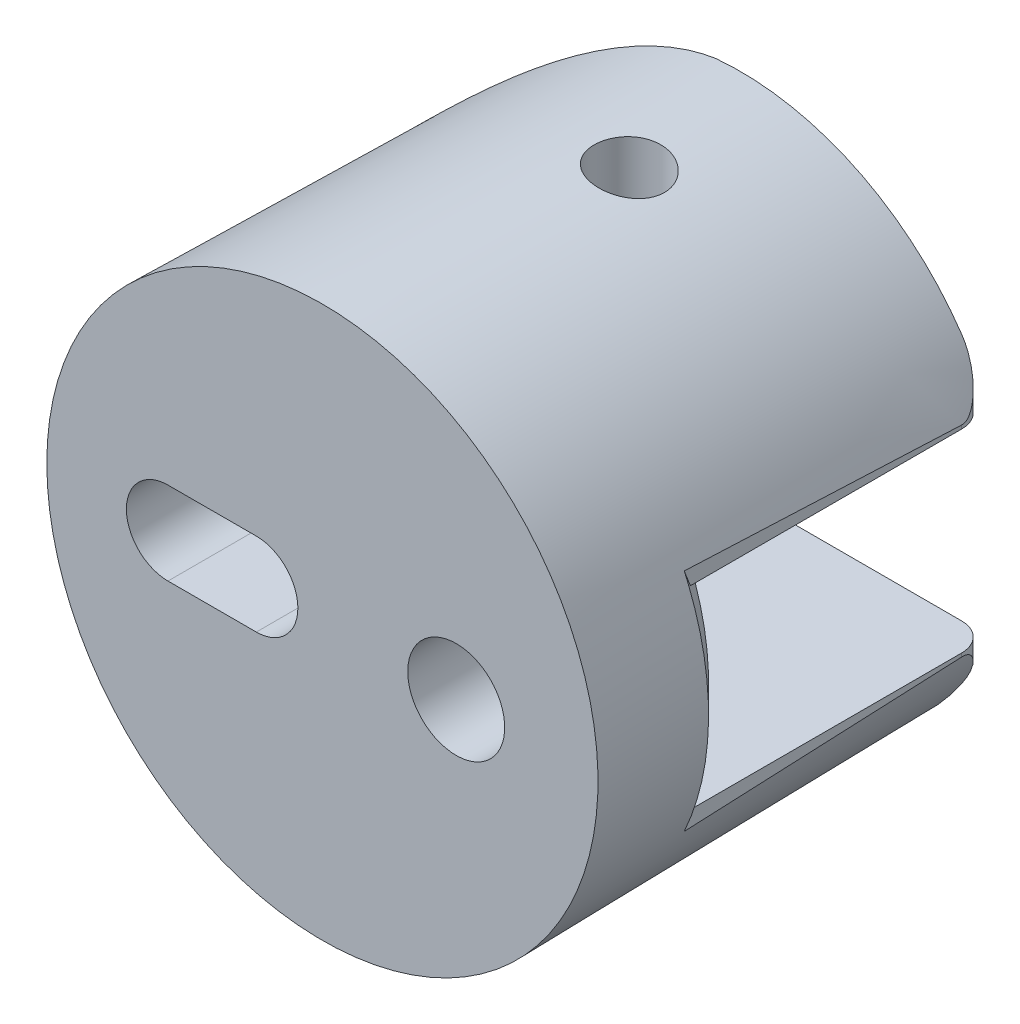
SolidWorks part; units mm, degrees
ref_plane "Plan de face" through (0, 0, 0) normal (0, 0, 1) x (1, 0, 0)
ref_plane "Plan de dessus" through (0, 0, 0) normal (0, 1, 0) x (1, 0, 0)
ref_plane "Plan de droite" through (0, 0, 0) normal (1, 0, 0) x (0, 0, -1)
sketch "Sketch1" plane through (0, 0, 0) normal (0, 0, 1) x (1, 0, 0)
  circle A0 centre (0, 0) radius 10
  dimension "D1" = 20
extrude "Boss-Extrude1" add sketch "Sketch1" along normal blind 18
sketch "Sketch2" plane through (0, 0, 0) normal (0, 1, 0) x (1, 0, 0)
  line L0 (-8, -10) -> (-16.4398, -10)
  line L1 (-16.4398, -10) -> (-16.4398, 10.405)
  line L2 (-16.4398, 10.405) -> (23.4224, 10.405)
  line L3 (23.4224, 10.405) -> (23.4224, -10)
  line L4 (23.4224, -10) -> (9, -10)
  line L5 (-10, 0) -> (-10, -18) construction
  line L6 (-10, -18) -> (10, -18) construction
  line L7 (9, -10) -> (9, 0)
  line L8 (10, 0) -> (-10, 0) construction
  line L9 (9, 0) -> (-0.88, 0)
  line L10 (-8, -10) -> (-7.3114, -5.8406)
  arc A0 (-7.3114, -5.8406) -> (-0.88, 0) centre (-0.4054, -6.9839) cw
  dimension "D5" = 7
  dimension "D1" = 2
  dimension "D2" = 8
  dimension "D3" = 17
  dimension "D4" = 9.88
  dimension "D6" = 80.6
  dimension "D7" = 4.216
extrude "Cut-Extrude1" cut sketch "Sketch2" against normal blind 18 and the other way blind 18 contours L10 A0 L9 L7 L4 L3 L2 L1 L0 region at (4.0327, 0, -1.4851)
sketch "Sketch3" plane through (0, 0, 0) normal (0, 1, 0) x (1, 0, 0)
  line L0 (-10, -18) -> (10, -18) construction
  line L1 (10, -18) -> (10, -10) construction
  circle A0 centre (1, -5) radius 1.25
  dimension "D3" = 2.5
  dimension "D1" = 13
  dimension "D2" = 9
extrude "Cut-Extrude2" cut sketch "Sketch3" against normal mid plane 24
sketch "Sketch4" plane through (0, 0, 18) normal (0, 0, 1) x (1, 0, 0)
  circle A0 centre (0, 0) radius 10
extrude "Cut-Extrude-Thin6" cut sketch "Sketch4" against normal blind 23.25 draft 1 thin contours A0 draft outward yes thin type one direction wall 10
sketch "Sketch5" plane through (0, 0, 0) normal (0, 1, 0) x (1, 0, 0)
  line L0 (9, -10) -> (9, 0) construction
  line L1 (-8, -10) -> (9, -10)
  line L2 (-8, -10) -> (-8, 5.0795)
  line L3 (-8, 5.0795) -> (9, 5.0795)
  line L4 (9, -10) -> (9, 5.0795)
extrude "Cut-Extrude3" cut sketch "Sketch5" against normal blind 3.5 and the other way blind 3.5
fillet "Fillet1" radius 1 2 edges at (9, 3.5399, 0) (9, -3.5399, 0)
sketch "Sketch6" plane through (0, 0, 0) normal (0, 1, 0) x (1, 0, 0)
  line L0 (-10, -18) -> (10, -18) construction
  line L1 (12.6946, -15.08) -> (-11.7994, -15.08)
  line L2 (12.6946, -15.08) -> (12.6946, -19.0549)
  line L3 (12.6946, -19.0549) -> (-11.7994, -19.0549)
  line L4 (-11.7994, -15.08) -> (-11.7994, -19.0549)
  dimension "D1" = 2.92
extrude "Cut-Extrude4" cut sketch "Sketch6" against normal mid plane 27.25
chamfer "Chamfer1" distance 1 angle 45 1 edges at (9.8604, 0, 10) first distance on face at (0.375, 0, 10)
sketch "Sketch7" plane through (0, 0, 10) normal (0, 0, -1) x (-1, 0, 0)
  line L0 (0, 0) -> (-8.0274, 0) construction
  line L1 (2.3859, 0) -> (5.5758, 0) construction
  line L2 (2.3859, 1.5) -> (5.5758, 1.5)
  line L3 (2.3859, -1.5) -> (5.5758, -1.5)
  circle A0 centre (-4.8309, 0) radius 1.75
  arc A2 (2.3859, 1.5) -> (2.3859, -1.5) centre (2.3859, 0) ccw
  arc A3 (5.5758, -1.5) -> (5.5758, 1.5) centre (5.5758, 0) ccw
  point P7 (3.9809, 0)
  point P12 (3.5135, 0)
  point P13 (2.3859, 0)
  dimension "D1" = 3.5
  dimension "D2" = 1.5
extrude "Cut-Extrude5" cut sketch "Sketch7" against normal blind 10
